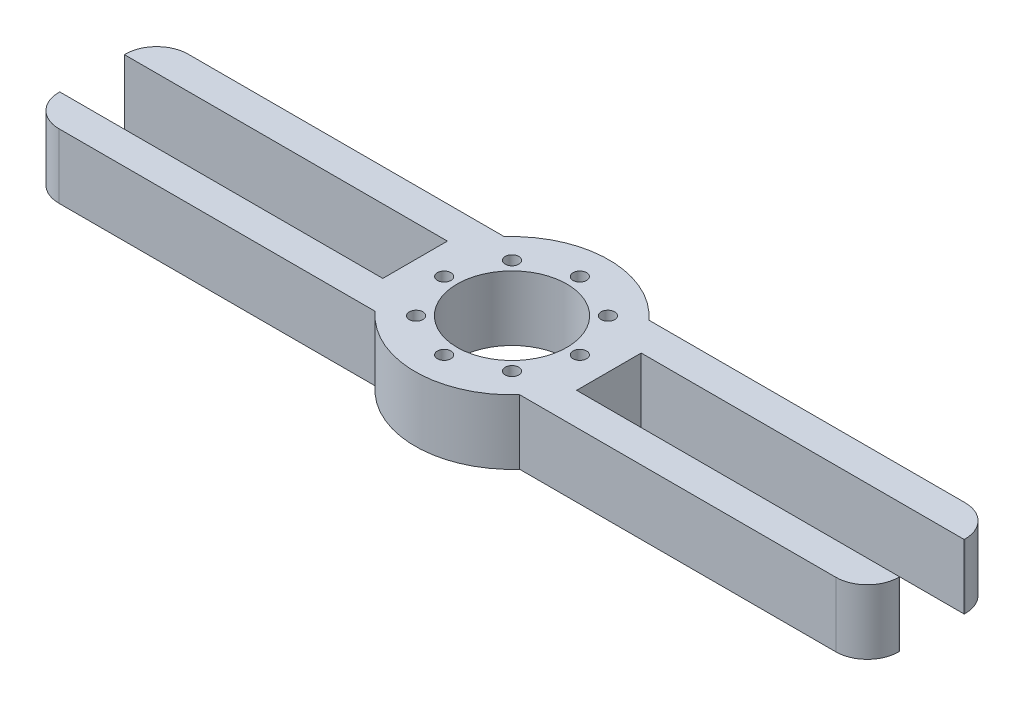
SolidWorks part; units mm, degrees
material "PTFE (general)"
ref_plane "Front Plane" through (0, 0, 0) normal (0, 0, 1) x (1, 0, 0)
ref_plane "Top Plane" through (0, 0, 0) normal (0, 1, 0) x (1, 0, 0)
ref_plane "Right Plane" through (0, 0, 0) normal (1, 0, 0) x (0, 0, -1)
sketch "Sketch1" plane through (0, 0, 0) normal (0, 1, 0) x (1, 0, 0)
  line L0 (22.3607, 20) -> (130, 20)
  line L1 (130, 20) -> (130, -20)
  line L2 (130, -20) -> (22.3607, -20)
  line L3 (0, -20) -> (0, 20)
  line L4 (0, 20) -> (0, 30)
  line L5 (0, -20) -> (0, -30)
  arc A0 (0, -30) -> (22.3607, -20) centre (0, 0) ccw
  arc A1 (22.3607, 20) -> (0, 30) centre (0, 0) ccw
  point P5 (0, 0)
  dimension "D1" = 60
  dimension "D2" = 130
  dimension "D3" = 40
extrude "Boss-Extrude1" add sketch "Sketch1" along normal blind 20
sketch "Sketch2" plane through (0, 20, 0) normal (0, 1, 0) x (1, 0, 0)
  line L0 (0, 17) -> (0, -17)
  line L1 (30, 10) -> (30, -10)
  line L2 (30, -10) -> (130, -10)
  line L3 (130, -10) -> (130, 10)
  line L4 (130, 10) -> (30, 10)
  line L6 (130, -20) -> (130, 20) construction
  arc A0 (0, -17) -> (0, 17) centre (0, 0) ccw
  point P1 (130, 0)
  point P8 (30, 0)
  dimension "D1" = 34
  dimension "D2" = 30
  dimension "D3" = 20
extrude "Cut-Extrude1" cut sketch "Sketch2" against normal up to surface (20 mm away) up to face at (51.1426, 0, 0)
fillet "Fillet1" radius 9.75 2 edges at (130, 10, 20) (130, 10, -20)
sketch "Sketch3" plane through (0, 0, -20) normal (0, 0, -1) x (-1, 0, 0)
  line L0 (0, 20) -> (0, 0) construction
  circle A0 centre (-40, 10) radius 2.5
  circle A1 centre (-50, 10) radius 2.5
  circle A2 centre (-60, 10) radius 2.5
  circle A3 centre (-70, 10) radius 2.5
  circle A4 centre (-80, 10) radius 2.5
  circle A5 centre (-90, 10) radius 2.5
  circle A6 centre (-100, 10) radius 2.5
  point P4 (0, 10)
  dimension "D2" = 5
  dimension "D1" = 40
  dimension "D3" = 7
extrude "Cut-Extrude2" [suppressed] cut sketch "Sketch3" against normal up to surface (40 mm away)
mirror "Mirror4" about plane through (0, 0, 0) normal (1, 0, 0) of "Boss-Extrude1", "Cut-Extrude1", "Fillet1", "Cut-Extrude2"
sketch "Sketch4" plane through (0, 20, 0) normal (0, 1, 0) x (1, 0, 0)
  circle A0 centre (21, 0) radius 2.1
  circle A1 centre (14.8492, -14.8492) radius 2.1
  circle A2 centre (0, -21) radius 2.1
  circle A3 centre (-14.8492, -14.8492) radius 2.1
  circle A4 centre (-21, 0) radius 2.1
  circle A5 centre (-14.8492, 14.8492) radius 2.1
  circle A6 centre (0, 21) radius 2.1
  circle A7 centre (14.8492, 14.8492) radius 2.1
  point P19 (0, 0)
  dimension "D2" = 4.2
  dimension "D1" = 21
  dimension "D3" = 8
extrude "Cut-Extrude3" cut sketch "Sketch4" against normal up to surface (20 mm away) up to face at (0, 0, 0)
sketch "Sketch5" plane through (0, 20, 0) normal (0, 1, 0) x (1, 0, 0)
  line L0 (0, 30) -> (0, -30) construction
  line L1 (-30, 0) -> (30, 0) construction
  line L2 (-30, 10) -> (-30, -10) construction
  line L3 (30, 10) -> (30, -10) construction
  arc A0 (22.3607, 20) -> (-22.3607, 20) centre (0, 0) ccw construction
  arc A1 (-22.3607, -20) -> (22.3607, -20) centre (0, 0) ccw construction
